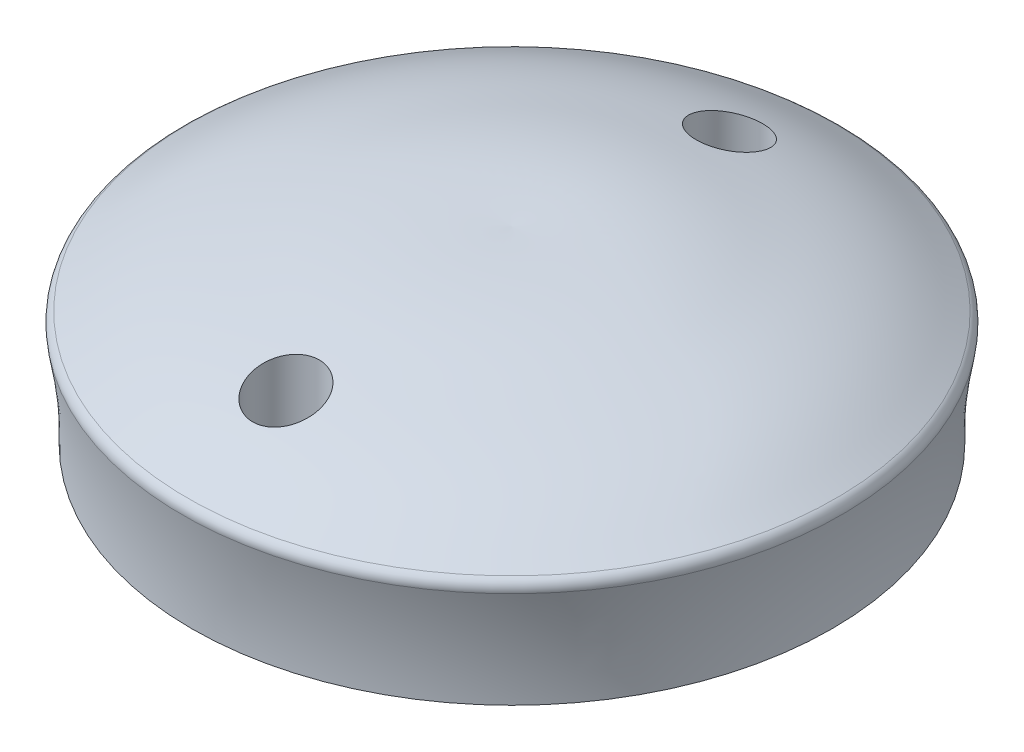
SolidWorks part; units mm, degrees
material "ABS"
ref_plane "Ebene vorne" through (0, 0, 0) normal (0, 0, 1) x (1, 0, 0)
ref_plane "Ebene oben" through (0, 0, 0) normal (0, 1, 0) x (1, 0, 0)
ref_plane "Ebene rechts" through (0, 0, 0) normal (1, 0, 0) x (0, 0, -1)
sketch "Skizze1" plane through (0, 0, 0) normal (1, 0, 0) x (0, 0, -1)
  line L0 (0.3802, 5.0989) -> (0.3802, 63) construction
  line L1 (30.2298, 2.0989) -> (0.3802, 2.0989)
  line L2 (30.2298, 20.0989) -> (30.2298, 2.0989) construction
  line L3 (0.3802, 10.0989) -> (0.3802, 5.0989)
  line L4 (0.3802, 2.0989) -> (0.3802, 5.0989)
  line L5 (0.3802, 10.0989) -> (29.2604, 10.0989)
  line L6 (0.3802, 27.0989) -> (0.3802, 10.0989)
  spline S0 degree 3 poles (0.3802, 27.0989) (8.6312, 27.5228) (14.312, 26.2021) (24.7476, 23.6366) (27.0768, 21.8661) (30.2298, 20.0989) knots 0 0 0 0 0.318831 0.418831 1 1 1 1
  spline S1 degree 3 poles (30.2298, 20.0989) (28.7981, 13.3242) (29.0428, 7.9803) (30.2298, 2.0989) knots 0 0 0 0 1 1 1 1
  dimension "D1" = 30
  dimension "D2" = 7
  dimension "D3" = 22
  dimension "D4" = 8
revolve "Rotation1" add sketch "Skizze1" angle 360 about L0 region at (0, 17.8633, -13.9624)
sketch "Skizze2" plane through (0, 10.0989, 0) normal (0, -1, 0) x (1, 0, 0)
  line L0 (0, -12.5) -> (0, 12.5) construction
  line L1 (5.15, 12.5) -> (-5.15, 12.5)
  line L2 (5.15, 12.5) -> (5.15, -12.5)
  line L3 (5.15, -12.5) -> (-5.15, -12.5)
  line L4 (-5.15, 12.5) -> (-5.15, -12.5)
  line L5 (5.15, 0) -> (-5.15, 0) construction
  circle A0 centre (0, -20) radius 1.5
  circle A1 centre (0, 20) radius 1.5
  point P8 (0, 0)
  dimension "D4" = 3
  dimension "D1" = 10.3
  dimension "D2" = 25
  dimension "D3" = 20
extrude "Schnitt-Linear austragen1" cut sketch "Skizze2" against normal blind 6.5 contours L1 L4 L3 L2 region at (0, 10.0989, 0)
extrude "Schnitt-Linear austragen2" cut sketch "Skizze2<3>" against normal blind 12 contours A1 | A0
sketch "Skizze2<3>" plane through (0, 10.0989, 0) normal (0, -1, 0) x (1, 0, 0) same geometry as "Skizze2"
fillet "Verrundung2" radius 1 1 edges at (0, 20.0989, -30.2298)
sketch "Skizze3" plane through (0, 10.0989, 0) normal (0, -1, 0) x (1, 0, 0)
  circle A0 centre (0, -20) radius 3
  circle A1 centre (0, 20) radius 3
  dimension "D1" = 6
  dimension "D2" = 6
extrude "Schnitt-Linear austragen3" cut sketch "Skizze3" against normal blind 20 from offset 3 offset against normal yes
